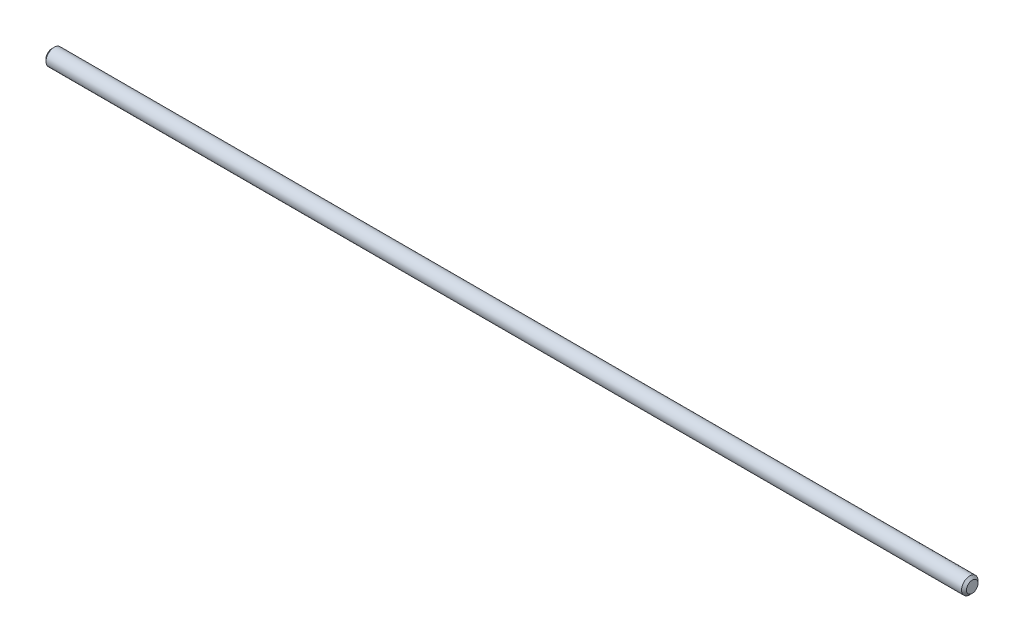
SolidWorks part; units mm, degrees
ref_plane "Front Plane" through (0, 0, 0) normal (0, 0, 1) x (1, 0, 0)
ref_plane "Top Plane" through (0, 0, 0) normal (0, 1, 0) x (1, 0, 0)
ref_plane "Right Plane" through (0, 0, 0) normal (1, 0, 0) x (0, 0, -1)
sketch "Sketch1" plane through (0, 0, 0) normal (0, 0, 1) x (1, 0, 0)
  line L0 (-177.8, 0) -> (177.8, 0) construction
  line L1 (177.8, 3.175) -> (177.8, -3.175) construction
  line L2 (-177.8, 3.175) -> (-177.8, -3.175) construction
  point P6 (173.355, -3.175)
  dimension "Thread Diameter" = 6.35
  dimension "Length" = 355.6
  dimension "D1" = 4.445
sketch "Sketch2" plane through (0, 0, 0) normal (1, 0, 0) x (0, 0, -1)
  circle A0 centre (0, 0) radius 3.175
extrude "Boss-Extrude1" add sketch "Sketch2" against normal up to vertex (177.8 mm away) and the other way up to vertex (177.8 mm away) up to point (-177.8, 0, 0) other way up to point (177.8, 0, 0)
cosmetic thread "Cosmetic Thread1" parameters "D2"=4.8387
sketch "Sketch3" plane through (177.8, 0, 0) normal (1, 0, 0) x (0, 0, -1)
  circle A1 centre (0, 0) radius 3.175
  circle A2 centre (0, 0) radius 3.175
  dimension "D1" = 0
curve "Helix/Spiral1" pitch 1.27 height 356.87 turns 281 parameters "Pitch"=1.27
chamfer "Chamfer1" distance 0.9525 angle 45 2 edges at (-177.8, 0, -3.175) (177.8, 0, -3.175)
sketch "Sketch4" plane through (0, 0, 0) normal (0, 0, 1) x (1, 0, 0)
  line L0 (177.7206, 3.3125) -> (178.3556, 2.2126) construction
  line L1 (178.3556, 2.2126) -> (178.9906, 3.3125) construction
  line L2 (178.9906, 3.3125) -> (177.7206, 3.3125) construction
  line L3 (178.3556, 3.3125) -> (178.3556, 3.175) construction
  line L4 (178.3556, 2.2126) -> (178.3556, 2.3501) construction
  line L5 (178.2763, 2.3501) -> (178.435, 2.3501) construction
  line L6 (177.8, 3.175) -> (178.9112, 3.175) construction
  line L7 (178.2763, 2.3501) -> (177.7603, 3.2437)
  line L8 (178.2763, 2.3501) -> (178.435, 2.3501)
  line L9 (177.7603, 3.2437) -> (178.9509, 3.2437)
  line L10 (178.9509, 3.2437) -> (178.435, 2.3501)
  point P13 (178.3556, 3.2437)
  dimension "D2" = 0.1588
sweep "Cut-Sweep3" [suppressed] cut profiles "Sketch4" path "Helix/Spiral1"
equation "\"D3@Helix/Spiral1\" = \"Length@Sketch1\"+\"Pitch@Helix/Spiral1\""
equation "\"D1@Chamfer1\" = \"Pitch@Helix/Spiral1\"*.75"
equation "\"D1@Sketch4\" = \"Pitch@Helix/Spiral1\""
equation "\"D2@Sketch4\" = \"D1@Sketch4\"/8"
equation "\"D1@Sketch1\" = \"Pitch@Helix/Spiral1\"*3.50"
